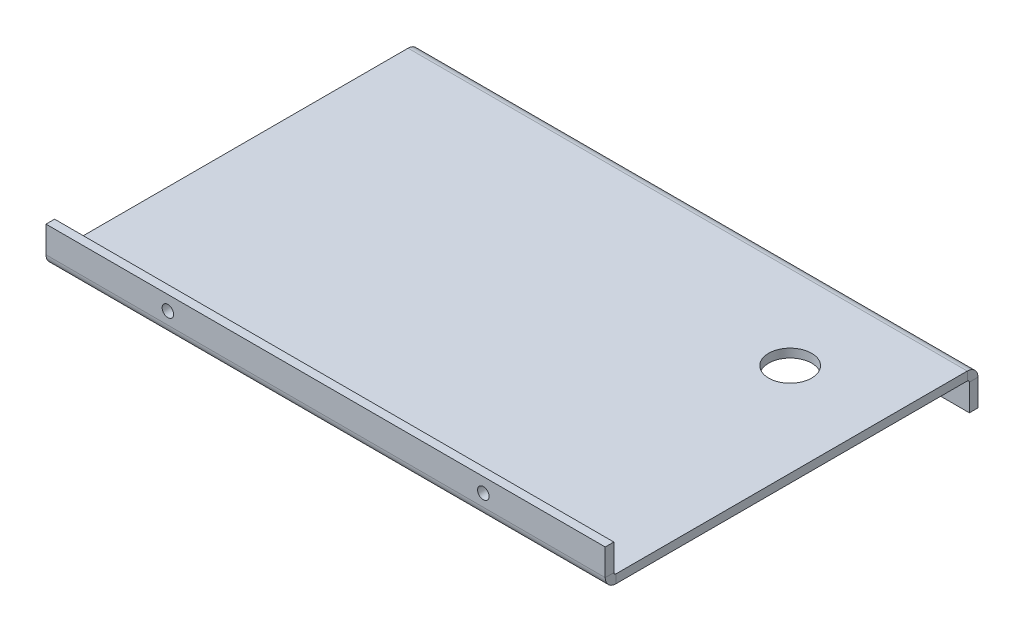
SolidWorks part; units mm, degrees
note: The reader was unsure of these and kept them because the rebuilt part matched: flange length of "边线-法兰1", "边线-法兰2".
ref_plane "前视基准面" through (0, 0, 0) normal (0, 0, 1) x (1, 0, 0)
ref_plane "上视基准面" through (0, 0, 0) normal (0, 1, 0) x (1, 0, 0)
ref_plane "右视基准面" through (0, 0, 0) normal (1, 0, 0) x (0, 0, -1)
sketch "草图1" plane through (0, 0, 0) normal (0, 1, 0) x (1, 0, 0)
  line L1 (-97.5, -65) -> (97.5, -65)
  line L2 (-97.5, -65) -> (-97.5, 65)
  line L3 (-97.5, 65) -> (97.5, 65)
  line L4 (97.5, -65) -> (97.5, 65)
  line L5 (-97.5, -65) -> (97.5, 65) construction
  line L6 (-97.5, 65) -> (97.5, -65) construction
  point P0 (0, 0)
  dimension "D1" = 130
  dimension "D2" = 195
base flange "基体-法兰1" sketch "草图1" thickness 3 reverse thickness direction no parameters "D1"=0.7366
edge flange "边线-法兰1" sketch "草图8" flange angle 90 flange length 10 flange position material inside bend radius 0.7366 thickness 3 relief rectangular parameters "D6"=10
sketch "草图8" plane through (0, 0, 65) normal (0, 0, 1) x (1, 0, 0)
  line L2 (-97.5, 0) -> (-97.5, 10)
  line L3 (-97.5, 10) -> (97.5, 10)
  line L4 (97.5, 10) -> (97.5, 0)
  line L7 (-97.5, 0) -> (97.5, 0) construction
  line L8 (-97.5, 0) -> (97.5, 0)
bend "边线折弯1" bend radius 0.7366 bend angle 90 parameters "D5"=1
edge flange "边线-法兰2" sketch "草图11" flange angle 90 flange length 10 flange position material inside bend radius 0.7366 thickness 3 relief rectangular parameters "D6"=10
sketch "草图11" plane through (0, -3, -65) normal (0, 0, -1) x (1, 0, 0)
  line L0 (97.5, 0) -> (-97.5, 0) construction
  line L1 (97.5, 0) -> (-97.5, 0)
  line L2 (-97.5, 0) -> (-97.5, 10)
  line L3 (-97.5, 10) -> (97.5, 10)
  line L4 (97.5, 10) -> (97.5, 0)
bend "边线折弯2" bend radius 0.7366 bend angle 90 parameters "D5"=2
sketch "草图12" plane through (0, 0, 65) normal (0, 0, 1) x (1, 0, 0)
  line L0 (0, 10) -> (0, 0) construction
  line L1 (97.5, 10) -> (-97.5, 10) construction
  circle A0 centre (-55, 5) radius 2
  circle A1 centre (55, 5) radius 2
  dimension "D1" = 4
  dimension "D2" = 5
  dimension "D3" = 110
extrude "切除-拉伸1" cut sketch "草图12" against normal blind 10 normal cut yes
sketch "草图13" plane through (0, 0, -65) normal (0, 0, -1) x (-1, 0, 0)
  line L0 (0, -3.7366) -> (0, -13) construction
  line L1 (-97.5, -3.7366) -> (97.5, -3.7366) construction
  line L2 (-97.5, -13) -> (97.5, -13) construction
  circle A0 centre (-55, -8) radius 2
  circle A1 centre (55, -8) radius 2
  dimension "D1" = 4
  dimension "D2" = 5
  dimension "D3" = 110
extrude "切除-拉伸2" cut sketch "草图13" against normal blind 10 normal cut yes
sketch "草图14" plane through (0, -3, 0) normal (0, -1, 0) x (1, 0, 0)
  line L0 (0, 61.2634) -> (0, -62) construction
  line L5 (97.5, 61.2634) -> (-97.5, 61.2634) construction
  line L6 (-97.5, -62) -> (97.5, -62) construction
  line L11 (97.5, -62) -> (-97.5, -62) construction
  circle A0 centre (65, -32) radius 7.5
  dimension "D1" = 15
  dimension "D2" = 65
  dimension "D3" = 30
extrude "切除-拉伸3" cut sketch "草图14" against normal up to next normal cut yes
sketch "折弯-线1" plane through (0, 0, 0) normal (0, 1, 0) x (1, 0, 0)
sketch "边界框1" plane through (0, 0, 0) normal (0, 1, 0) x (1, 0, 0)
sheet metal parameters "钣金6" thickness 3 parameters "D1"=0.7366
flat pattern "平板型式6" [suppressed]
sketch "折弯-线2" plane through (0, 0, 0) normal (0, 1, 0) x (1, 0, 0)
sketch "边界框2" [suppressed] plane through (0, 0, 0) normal (0, 1, 0) x (1, 0, 0)
sheet metal parameters "钣金7" thickness 3 parameters "D1"=0.7366
flat pattern "平板型式6" [suppressed]
sketch "折弯-线2" plane through (0, 0, 0) normal (0, 1, 0) x (1, 0, 0)
sketch "边界框2" [suppressed] plane through (0, 0, 0) normal (0, 1, 0) x (1, 0, 0)
bend of the flat pattern "展平-<边线折弯1>1"
sheet metal parameters "钣金8" thickness 3 parameters "D1"=0.7366
flat pattern "平板型式6" [suppressed]
sketch "折弯-线2" plane through (0, 0, 0) normal (0, 1, 0) x (1, 0, 0)
sketch "边界框2" [suppressed] plane through (0, 0, 0) normal (0, 1, 0) x (1, 0, 0)
bend of the flat pattern "展平-<边线折弯1>1"
bend of the flat pattern "展平-<边线折弯2>1"
sheet metal parameters "钣金9" thickness 3 parameters "D1"=0.7366
flat pattern "平板型式6" [suppressed]
sketch "折弯-线2" plane through (0, 0, 0) normal (0, 1, 0) x (1, 0, 0)
sketch "边界框2" [suppressed] plane through (0, 0, 0) normal (0, 1, 0) x (1, 0, 0)
bend of the flat pattern "展平-<边线折弯1>1"
bend of the flat pattern "展平-<边线折弯2>1"
sheet metal parameters "钣金10" thickness 3 parameters "D1"=0.7366
flat pattern "平板型式6" [suppressed]
sketch "折弯-线2" plane through (0, 0, 0) normal (0, 1, 0) x (1, 0, 0)
sketch "边界框2" [suppressed] plane through (0, 0, 0) normal (0, 1, 0) x (1, 0, 0)
bend of the flat pattern "展平-<边线折弯1>1"
bend of the flat pattern "展平-<边线折弯2>1"
sheet metal parameters "钣金11" thickness 3 parameters "D1"=0.7366
flat pattern "平板型式6" [suppressed]
sketch "折弯-线2" plane through (0, 0, 0) normal (0, 1, 0) x (1, 0, 0)
sketch "边界框2" [suppressed] plane through (0, 0, 0) normal (0, 1, 0) x (1, 0, 0)
bend of the flat pattern "展平-<边线折弯1>1"
bend of the flat pattern "展平-<边线折弯2>1"
